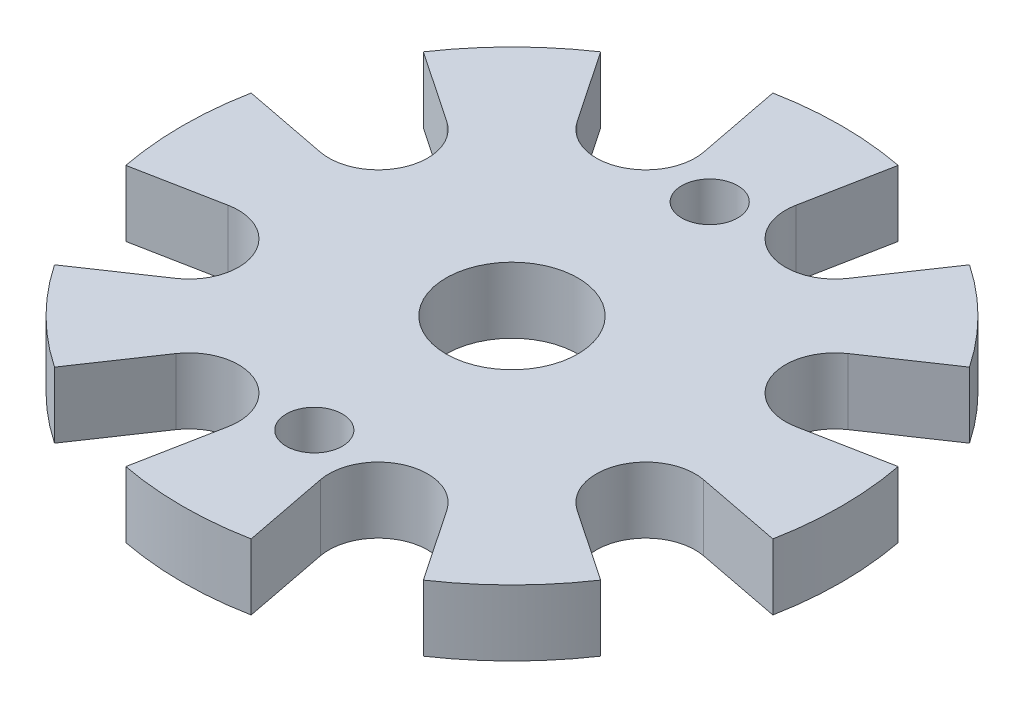
SolidWorks part; units mm, degrees
material "Acrylic (Medium-high impact)"
ref_plane "Front Plane" through (0, 0, 0) normal (0, 0, 1) x (1, 0, 0)
ref_plane "Top Plane" through (0, 0, 0) normal (0, 1, 0) x (1, 0, 0)
ref_plane "Right Plane" through (0, 0, 0) normal (1, 0, 0) x (0, 0, -1)
sketch "Sketch1" plane through (0, 0, 0) normal (0, 1, 0) x (1, 0, 0)
  circle A0 centre (0, 0) radius 20
  dimension "D1" = 40
sketch "Sketch2" plane through (0, 0, 0) normal (0, 1, 0) x (1, 0, 0)
  line L0 (-11.8283, 0) -> (13.8416, 0) construction
  circle A0 centre (0, 0) radius 4
  circle A1 centre (0, 12) radius 1.7
  circle A2 centre (0, -12) radius 1.7
  dimension "D1" = 8
  dimension "D2" = 3.4
  dimension "D3" = 12
extrude "Boss-Extrude1" add sketch "Sketch1" along normal blind 4
extrude "Cut-Extrude1" cut sketch "Sketch2" along normal up to next
sketch "Sketch3" plane through (0, 0, 0) normal (0, 1, 0) x (1, 0, 0)
  line L0 (0, 0) -> (0, 20) construction
  line L1 (0, 0) -> (7.6537, 18.4776) construction
  line L2 (3.8035, 19.635) -> (2.795, 14.4287)
  line L3 (11.1946, 16.5735) -> (8.2263, 12.179)
  line L4 (2.795, 14.4287) -> (8.2263, 12.179) construction
  circle A1 centre (0, 0) radius 4 construction
  circle A2 centre (0, 0) radius 20 construction
  arc A3 (2.795, 14.4287) -> (8.2263, 12.179) centre (5.7403, 13.8582) ccw
  arc A4 (3.8035, 19.635) -> (11.1946, 16.5735) centre (0, 0) cw
  point P0 (0, 0)
  dimension "D2" = 3
  dimension "D1" = 15
  dimension "D3" = 22.5
extrude "Cut-Extrude3" cut sketch "Sketch3" along normal up to next contours A4 L2 A3 L3 region at (6.2907, 0, -15.187)
pattern_circular "CirPattern1" count 8 over 360 about axis through (0, 4, 0) along (0, 1, 0) of "Cut-Extrude3"
